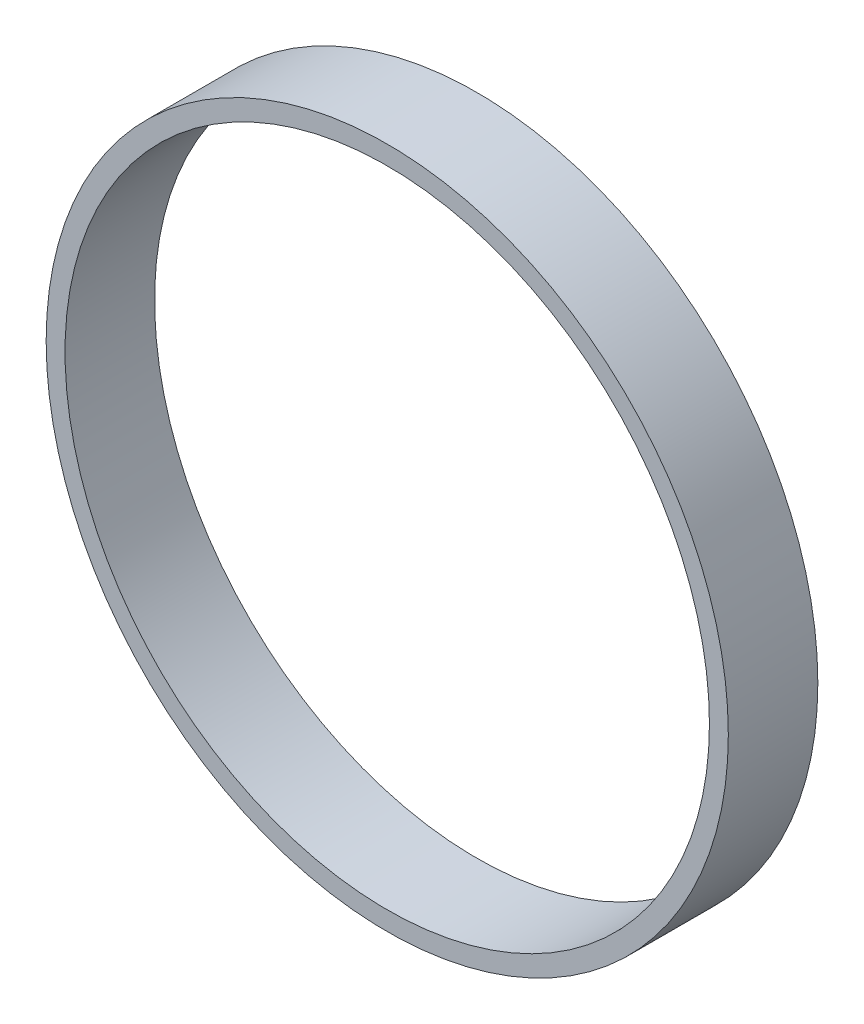
SolidWorks part; units mm, degrees
ref_plane "Front Plane" through (0, 0, 0) normal (0, 0, 1) x (1, 0, 0)
ref_plane "Top Plane" through (0, 0, 0) normal (0, 1, 0) x (1, 0, 0)
ref_plane "Right Plane" through (0, 0, 0) normal (1, 0, 0) x (0, 0, -1)
sketch "Sketch1" plane through (0, 0, 0) normal (0, 0, 1) x (1, 0, 0)
  circle A0 centre (0, 0) radius 38.1
  circle A1 centre (0, 0) radius 35.99
  dimension "D1" = 76.2
  dimension "D2" = 71.98
extrude "Boss-Extrude1" add sketch "Sketch1" along normal blind 10
